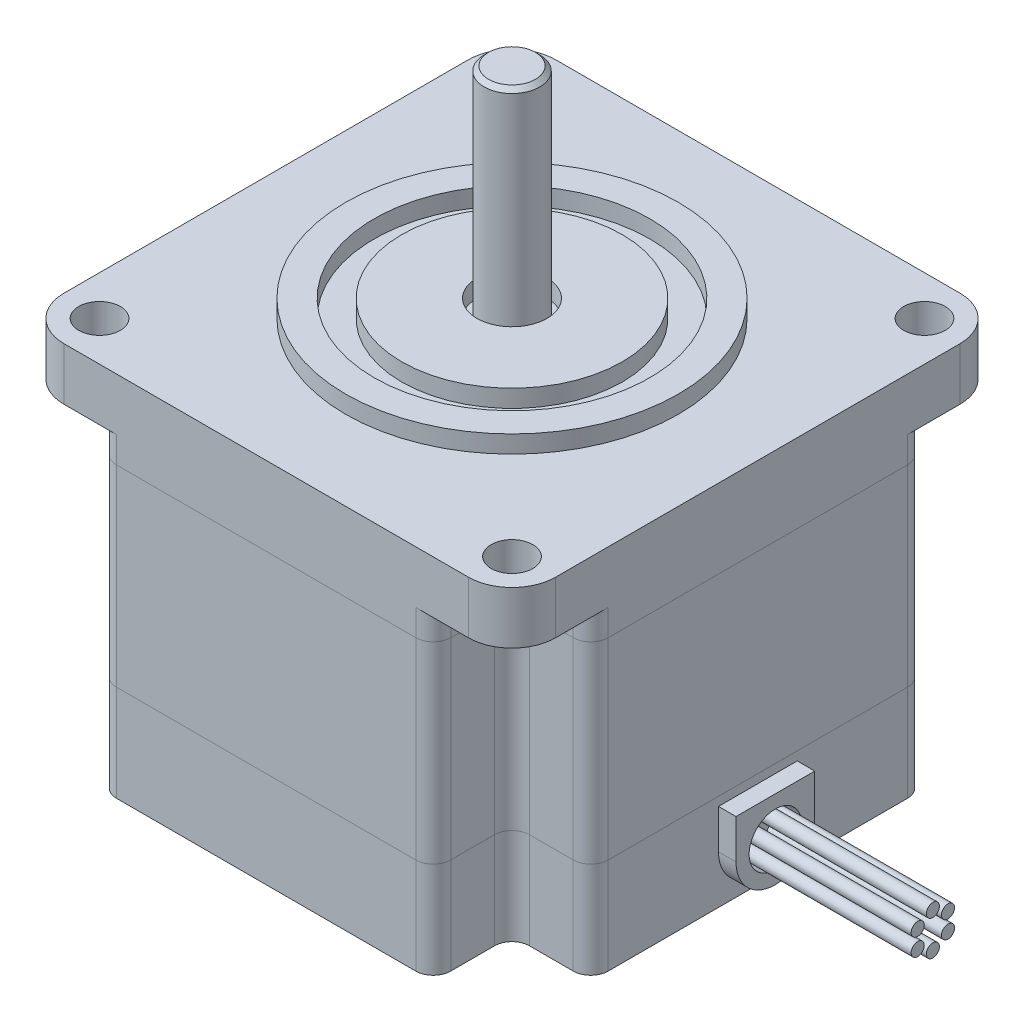
SolidWorks part; units mm, degrees
other "Camera1"
ref_plane "Front Plane" through (0, 0, 0) normal (0, 0, 1) x (1, 0, 0)
ref_plane "Top Plane" through (0, 0, 0) normal (0, 1, 0) x (1, 0, 0)
ref_plane "Right Plane" through (0, 0, 0) normal (1, 0, 0) x (0, 0, -1)
sketch "Sketch1" plane through (0, 0, 0) normal (0, 1, 0) x (1, 0, 0)
  line L1 (28.1, -28.1) -> (-28.1, -28.1)
  line L2 (28.1, -28.1) -> (28.1, 28.1)
  line L3 (28.1, 28.1) -> (-28.1, 28.1)
  line L4 (-28.1, -28.1) -> (-28.1, 28.1)
  line L5 (0, 28.1) -> (0, -28.1) construction
  line L6 (21, 0) -> (-28.1, 0) construction
  circle A0 centre (23.57, 23.57) radius 2.375
  circle A1 centre (23.57, -23.57) radius 2.375
  circle A2 centre (-23.57, -23.57) radius 2.375
  circle A3 centre (-23.57, 23.57) radius 2.375
  point P0 (0, 0)
  point P1 (-28.1, 28.1)
  point P6 (0, 28.1)
  point P7 (-28.1, 0)
  point P15 (0, 0)
  point P19 (0, -28.1)
  dimension "D2" = 4.75
  dimension "D1" = 56.2
  dimension "D4" = 47.14
  dimension "D3" = 4
extrude "Boss-Extrude2" add sketch "Sketch1" along normal blind 11
sketch "Sketch2" plane through (0, 11, 0) normal (0, 1, 0) x (1, 0, 0)
  line L8 (28.1, 28.1) -> (-28.1, 28.1)
  line L10 (-28.1, 28.1) -> (-28.1, -28.1)
  line L12 (-28.1, -28.1) -> (28.1, -28.1)
  line L14 (28.1, -28.1) -> (28.1, 28.1)
  line L16 (28.1, 28.1) -> (-28.1, 28.1)
  line L18 (-28.1, 28.1) -> (-28.1, -28.1)
  line L20 (-28.1, -28.1) -> (28.1, -28.1)
  line L22 (28.1, -28.1) -> (28.1, 28.1)
  circle A0 centre (-23.57, -23.57) radius 2.375 construction
  circle A1 centre (23.57, -23.57) radius 2.375 construction
  circle A2 centre (23.57, 23.57) radius 2.375 construction
  circle A3 centre (-23.57, 23.57) radius 2.375 construction
  circle A4 centre (-23.57, -23.57) radius 2.375
  circle A5 centre (23.57, -23.57) radius 2.375
  circle A6 centre (23.57, 23.57) radius 2.375
  circle A7 centre (-23.57, 23.57) radius 2.375
  dimension "D1" = 0
extrude "Boss-Extrude3" add sketch "Sketch2" along normal blind 22 separate body
sketch "Sketch3" plane through (0, 33, 0) normal (0, 1, 0) x (1, 0, 0)
  line L9 (28.1, 28.1) -> (-28.1, 28.1)
  line L11 (-28.1, 28.1) -> (-28.1, -28.1)
  line L13 (-28.1, -28.1) -> (28.1, -28.1)
  line L15 (28.1, -28.1) -> (28.1, 28.1)
  line L17 (28.1, 28.1) -> (-28.1, 28.1)
  line L19 (-28.1, 28.1) -> (-28.1, -28.1)
  line L21 (-28.1, -28.1) -> (28.1, -28.1)
  line L23 (28.1, -28.1) -> (28.1, 28.1)
  circle A0 centre (23.57, 23.57) radius 2.375 construction
  circle A1 centre (23.57, -23.57) radius 2.375 construction
  circle A2 centre (-23.57, -23.57) radius 2.375 construction
  circle A3 centre (-23.57, 23.57) radius 2.375 construction
  circle A4 centre (23.57, 23.57) radius 2.375
  circle A5 centre (23.57, -23.57) radius 2.375
  circle A6 centre (-23.57, -23.57) radius 2.375
  circle A7 centre (-23.57, 23.57) radius 2.375
  point P4 (0, 0)
  point P5 (0, 0)
  point P6 (0, 0)
  point P7 (0, 0)
  point P8 (0, 0)
  dimension "D1" = 0
extrude "Boss-Extrude4" add sketch "Sketch3" along normal blind 9 separate body
sketch "Sketch4" plane through (28.1, 0, 0) normal (1, 0, 0) x (0, 0, -1)
  line L1 (0, 0) -> (0, 11) construction
  line L2 (-28.1, 11) -> (28.1, 11) construction
  line L3 (-4.5, 5.5) -> (-4.5, 10)
  line L4 (-4.5, 10) -> (4.5, 10)
  line L5 (4.5, 5.5) -> (4.5, 10)
  arc A0 (-4.5, 5.5) -> (4.5, 5.5) centre (0, 5.5) ccw
  circle A1 centre (0, 5.5) radius 3
  point P11 (0, 10)
  dimension "D1" = 6
  dimension "D2" = 9
extrude "Boss-Extrude5" add sketch "Sketch4" along normal blind 2 separate body
sketch "Sketch5" plane through (28.1, 0, 0) normal (1, 0, 0) x (0, 0, -1)
  circle A0 centre (-1.7321, 4.5) radius 0.75
  circle A1 centre (0, 3.5) radius 0.75
  circle A2 centre (-1.7321, 6.5) radius 0.75
  circle A3 centre (0, 7.5) radius 0.75
  circle A4 centre (1.7321, 6.5) radius 0.75
  circle A5 centre (1.7321, 4.5) radius 0.75
  circle A6 centre (0, 5.5) radius 2 construction
  point P15 (0, 5.5)
  dimension "D1" = 1.5
  dimension "D3" = 4
  dimension "D2" = 6
extrude "Boss-Extrude6" add sketch "Sketch5" along normal blind 20 separate body contours A2 | A0 | A1 | A5 | A4 | A3
sketch "Sketch6" plane through (0, 42, 0) normal (0, 1, 0) x (1, 0, 0)
  circle A0 centre (0, 0) radius 12.6
  circle A1 centre (0, 0) radius 19
  circle A2 centre (0, 0) radius 15.75
  circle A3 centre (0, 0) radius 4
  dimension "D1" = 25.2
  dimension "D2" = 38
  dimension "D3" = 31.5
  dimension "D4" = 8
extrude "Boss-Extrude7" add sketch "Sketch6" along normal blind 2 contours A1 A2 | A0 region at (-12.2436, 42, 0) region at (-18.4626, 42, 0)
sketch "Sketch7" plane through (0, 42, 0) normal (0, 1, 0) x (1, 0, 0)
  circle A0 centre (0, 0) radius 3.175
  dimension "D1" = 6.35
extrude "Boss-Extrude8" add sketch "Sketch7" along normal blind 25 separate body
sketch "Sketch8" plane through (0, 67, 0) normal (0, 1, 0) x (1, 0, 0)
  circle A0 centre (0, 0) radius 7.675
  circle A1 centre (0, 0) radius 3.175
  circle A2 centre (0, 0) radius 3.175
  dimension "D2" = 15.35
  dimension "D1" = 0
extrude "Boss-Extrude9" [suppressed] add sketch "Sketch8" against normal blind 10 separate body
sketch "Sketch9" [suppressed] plane through (0, 56, 0) normal (0, -1, 0) x (1, 0, 0)
  circle A0 centre (0, 0) radius 10
  dimension "D1" = 20
extrude "Boss-Extrude10" [suppressed] add sketch "Sketch9" against normal blind 1
sketch "Sketch10" [suppressed] plane through (0, 66, 0) normal (0, 1, 0) x (1, 0, 0)
  line L0 (0, 7.675) -> (0, 8.675) construction
  line L1 (-0.6, 7.6515) -> (-0.3, 8.4658)
  line L2 (0.6, 7.6515) -> (0.3, 8.4658)
  line L3 (1.1177, 7.5932) -> (1.5913, 8.3203)
  line L4 (2.2876, 7.3262) -> (2.1763, 8.1868)
  line L5 (1.7078, 7.4826) -> (1.9304, 8.4575) construction
  line L6 (2.7793, 7.1541) -> (3.4029, 7.7576)
  line L7 (3.8604, 6.6334) -> (3.9435, 7.4973)
  line L8 (3.3301, 6.9149) -> (3.7639, 7.8159) construction
  line L9 (4.3015, 6.3563) -> (5.0438, 6.8059)
  line L10 (5.2397, 5.6081) -> (5.5129, 6.4318)
  line L11 (4.7853, 6.0006) -> (5.4088, 6.7824) construction
  line L12 (5.6081, 5.2397) -> (6.4318, 5.5129)
  line L13 (6.3563, 4.3015) -> (6.8059, 5.0438)
  line L14 (6.0006, 4.7853) -> (6.7824, 5.4088) construction
  line L15 (6.6334, 3.8604) -> (7.4973, 3.9435)
  line L16 (7.1541, 2.7793) -> (7.7576, 3.4029)
  line L17 (6.9149, 3.3301) -> (7.8159, 3.7639) construction
  line L18 (7.3262, 2.2876) -> (8.1868, 2.1763)
  line L19 (7.5932, 1.1177) -> (8.3203, 1.5913)
  line L20 (7.4826, 1.7078) -> (8.4575, 1.9304) construction
  line L21 (7.6515, 0.6) -> (8.4658, 0.3)
  line L22 (7.6515, -0.6) -> (8.4658, -0.3)
  line L23 (7.675, 0) -> (8.675, 0) construction
  line L24 (7.5932, -1.1177) -> (8.3203, -1.5913)
  line L25 (7.3262, -2.2876) -> (8.1868, -2.1763)
  line L26 (7.4826, -1.7078) -> (8.4575, -1.9304) construction
  line L27 (7.1541, -2.7793) -> (7.7576, -3.4029)
  line L28 (6.6334, -3.8604) -> (7.4973, -3.9435)
  line L29 (6.9149, -3.3301) -> (7.8159, -3.7639) construction
  line L30 (6.3563, -4.3015) -> (6.8059, -5.0438)
  line L31 (5.6081, -5.2397) -> (6.4318, -5.5129)
  line L32 (6.0006, -4.7853) -> (6.7824, -5.4088) construction
  line L33 (5.2397, -5.6081) -> (5.5129, -6.4318)
  line L34 (4.3015, -6.3563) -> (5.0438, -6.8059)
  line L35 (4.7853, -6.0006) -> (5.4088, -6.7824) construction
  line L36 (3.8604, -6.6334) -> (3.9435, -7.4973)
  line L37 (2.7793, -7.1541) -> (3.4029, -7.7576)
  line L38 (3.3301, -6.9149) -> (3.7639, -7.8159) construction
  line L39 (2.2876, -7.3262) -> (2.1763, -8.1868)
  line L40 (1.1177, -7.5932) -> (1.5913, -8.3203)
  line L41 (1.7078, -7.4826) -> (1.9304, -8.4575) construction
  line L42 (0.6, -7.6515) -> (0.3, -8.4658)
  line L43 (-0.6, -7.6515) -> (-0.3, -8.4658)
  line L44 (0, -7.675) -> (0, -8.675) construction
  line L45 (-1.1177, -7.5932) -> (-1.5913, -8.3203)
  line L46 (-2.2876, -7.3262) -> (-2.1763, -8.1868)
  line L47 (-1.7078, -7.4826) -> (-1.9304, -8.4575) construction
  line L48 (-2.7793, -7.1541) -> (-3.4029, -7.7576)
  line L49 (-3.8604, -6.6334) -> (-3.9435, -7.4973)
  line L50 (-3.3301, -6.9149) -> (-3.7639, -7.8159) construction
  line L51 (-4.3015, -6.3563) -> (-5.0438, -6.8059)
  line L52 (-5.2397, -5.6081) -> (-5.5129, -6.4318)
  line L53 (-4.7853, -6.0006) -> (-5.4088, -6.7824) construction
  line L54 (-5.6081, -5.2397) -> (-6.4318, -5.5129)
  line L55 (-6.3563, -4.3015) -> (-6.8059, -5.0438)
  line L56 (-6.0006, -4.7853) -> (-6.7824, -5.4088) construction
  line L57 (-6.6334, -3.8604) -> (-7.4973, -3.9435)
  line L58 (-7.1541, -2.7793) -> (-7.7576, -3.4029)
  line L59 (-6.9149, -3.3301) -> (-7.8159, -3.7639) construction
  line L60 (-7.3262, -2.2876) -> (-8.1868, -2.1763)
  line L61 (-7.5932, -1.1177) -> (-8.3203, -1.5913)
  line L62 (-7.4826, -1.7078) -> (-8.4575, -1.9304) construction
  line L63 (-7.6515, -0.6) -> (-8.4658, -0.3)
  line L64 (-7.6515, 0.6) -> (-8.4658, 0.3)
  line L65 (-7.675, 0) -> (-8.675, 0) construction
  line L66 (-7.5932, 1.1177) -> (-8.3203, 1.5913)
  line L67 (-7.3262, 2.2876) -> (-8.1868, 2.1763)
  line L68 (-7.4826, 1.7078) -> (-8.4575, 1.9304) construction
  line L69 (-7.1541, 2.7793) -> (-7.7576, 3.4029)
  line L70 (-6.6334, 3.8604) -> (-7.4973, 3.9435)
  line L71 (-6.9149, 3.3301) -> (-7.8159, 3.7639) construction
  line L72 (-6.3563, 4.3015) -> (-6.8059, 5.0438)
  line L73 (-5.6081, 5.2397) -> (-6.4318, 5.5129)
  line L74 (-6.0006, 4.7853) -> (-6.7824, 5.4088) construction
  line L75 (-5.2397, 5.6081) -> (-5.5129, 6.4318)
  line L76 (-4.3015, 6.3563) -> (-5.0438, 6.8059)
  line L77 (-4.7853, 6.0006) -> (-5.4088, 6.7824) construction
  line L78 (-3.8604, 6.6334) -> (-3.9435, 7.4973)
  line L79 (-2.7793, 7.1541) -> (-3.4029, 7.7576)
  line L80 (-3.3301, 6.9149) -> (-3.7639, 7.8159) construction
  line L81 (-2.2876, 7.3262) -> (-2.1763, 8.1868)
  line L82 (-1.1177, 7.5932) -> (-1.5913, 8.3203)
  line L83 (-1.7078, 7.4826) -> (-1.9304, 8.4575) construction
  circle A0 centre (0, 0) radius 8.675 construction
  circle A1 centre (0, 0) radius 7.675 construction
  circle A2 centre (0, 0) radius 7.675 construction
  arc A3 (-0.3, 8.4658) -> (0, 8.675) centre (0, 8.3553) cw
  circle A4 centre (0, 0) radius 7.675
  arc A5 (0.6, 7.6515) -> (-0.6, 7.6515) centre (0, 0) ccw
  arc A6 (0.3, 8.4658) -> (0, 8.675) centre (0, 8.3553) ccw
  arc A7 (1.5913, 8.3203) -> (1.9304, 8.4575) centre (1.8592, 8.1458) cw
  arc A8 (2.2876, 7.3262) -> (1.1177, 7.5932) centre (0, 0) ccw
  arc A9 (2.1763, 8.1868) -> (1.9304, 8.4575) centre (1.8592, 8.1458) ccw
  arc A10 (3.4029, 7.7576) -> (3.7639, 7.8159) centre (3.6252, 7.5279) cw
  arc A11 (3.8604, 6.6334) -> (2.7793, 7.1541) centre (0, 0) ccw
  arc A12 (3.9435, 7.4973) -> (3.7639, 7.8159) centre (3.6252, 7.5279) ccw
  arc A13 (5.0438, 6.8059) -> (5.4088, 6.7824) centre (5.2094, 6.5324) cw
  arc A14 (5.2397, 5.6081) -> (4.3015, 6.3563) centre (0, 0) ccw
  arc A15 (5.5129, 6.4318) -> (5.4088, 6.7824) centre (5.2094, 6.5324) ccw
  arc A16 (6.4318, 5.5129) -> (6.7824, 5.4088) centre (6.5324, 5.2094) cw
  arc A17 (6.3563, 4.3015) -> (5.6081, 5.2397) centre (0, 0) ccw
  arc A18 (6.8059, 5.0438) -> (6.7824, 5.4088) centre (6.5324, 5.2094) ccw
  arc A19 (7.4973, 3.9435) -> (7.8159, 3.7639) centre (7.5279, 3.6252) cw
  arc A20 (7.1541, 2.7793) -> (6.6334, 3.8604) centre (0, 0) ccw
  arc A21 (7.7576, 3.4029) -> (7.8159, 3.7639) centre (7.5279, 3.6252) ccw
  arc A22 (8.1868, 2.1763) -> (8.4575, 1.9304) centre (8.1458, 1.8592) cw
  arc A23 (7.5932, 1.1177) -> (7.3262, 2.2876) centre (0, 0) ccw
  arc A24 (8.3203, 1.5913) -> (8.4575, 1.9304) centre (8.1458, 1.8592) ccw
  arc A25 (8.4658, 0.3) -> (8.675, 0) centre (8.3553, 0) cw
  arc A26 (7.6515, -0.6) -> (7.6515, 0.6) centre (0, 0) ccw
  arc A27 (8.4658, -0.3) -> (8.675, 0) centre (8.3553, 0) ccw
  arc A28 (8.3203, -1.5913) -> (8.4575, -1.9304) centre (8.1458, -1.8592) cw
  arc A29 (7.3262, -2.2876) -> (7.5932, -1.1177) centre (0, 0) ccw
  arc A30 (8.1868, -2.1763) -> (8.4575, -1.9304) centre (8.1458, -1.8592) ccw
  arc A31 (7.7576, -3.4029) -> (7.8159, -3.7639) centre (7.5279, -3.6252) cw
  arc A32 (6.6334, -3.8604) -> (7.1541, -2.7793) centre (0, 0) ccw
  arc A33 (7.4973, -3.9435) -> (7.8159, -3.7639) centre (7.5279, -3.6252) ccw
  arc A34 (6.8059, -5.0438) -> (6.7824, -5.4088) centre (6.5324, -5.2094) cw
  arc A35 (5.6081, -5.2397) -> (6.3563, -4.3015) centre (0, 0) ccw
  arc A36 (6.4318, -5.5129) -> (6.7824, -5.4088) centre (6.5324, -5.2094) ccw
  arc A37 (5.5129, -6.4318) -> (5.4088, -6.7824) centre (5.2094, -6.5324) cw
  arc A38 (4.3015, -6.3563) -> (5.2397, -5.6081) centre (0, 0) ccw
  arc A39 (5.0438, -6.8059) -> (5.4088, -6.7824) centre (5.2094, -6.5324) ccw
  arc A40 (3.9435, -7.4973) -> (3.7639, -7.8159) centre (3.6252, -7.5279) cw
  arc A41 (2.7793, -7.1541) -> (3.8604, -6.6334) centre (0, 0) ccw
  arc A42 (3.4029, -7.7576) -> (3.7639, -7.8159) centre (3.6252, -7.5279) ccw
  arc A43 (2.1763, -8.1868) -> (1.9304, -8.4575) centre (1.8592, -8.1458) cw
  arc A44 (1.1177, -7.5932) -> (2.2876, -7.3262) centre (0, 0) ccw
  arc A45 (1.5913, -8.3203) -> (1.9304, -8.4575) centre (1.8592, -8.1458) ccw
  arc A46 (0.3, -8.4658) -> (0, -8.675) centre (0, -8.3553) cw
  arc A47 (-0.6, -7.6515) -> (0.6, -7.6515) centre (0, 0) ccw
  arc A48 (-0.3, -8.4658) -> (0, -8.675) centre (0, -8.3553) ccw
  arc A49 (-1.5913, -8.3203) -> (-1.9304, -8.4575) centre (-1.8592, -8.1458) cw
  arc A50 (-2.2876, -7.3262) -> (-1.1177, -7.5932) centre (0, 0) ccw
  arc A51 (-2.1763, -8.1868) -> (-1.9304, -8.4575) centre (-1.8592, -8.1458) ccw
  arc A52 (-3.4029, -7.7576) -> (-3.7639, -7.8159) centre (-3.6252, -7.5279) cw
  arc A53 (-3.8604, -6.6334) -> (-2.7793, -7.1541) centre (0, 0) ccw
  arc A54 (-3.9435, -7.4973) -> (-3.7639, -7.8159) centre (-3.6252, -7.5279) ccw
  arc A55 (-5.0438, -6.8059) -> (-5.4088, -6.7824) centre (-5.2094, -6.5324) cw
  arc A56 (-5.2397, -5.6081) -> (-4.3015, -6.3563) centre (0, 0) ccw
  arc A57 (-5.5129, -6.4318) -> (-5.4088, -6.7824) centre (-5.2094, -6.5324) ccw
  arc A58 (-6.4318, -5.5129) -> (-6.7824, -5.4088) centre (-6.5324, -5.2094) cw
  arc A59 (-6.3563, -4.3015) -> (-5.6081, -5.2397) centre (0, 0) ccw
  arc A60 (-6.8059, -5.0438) -> (-6.7824, -5.4088) centre (-6.5324, -5.2094) ccw
  arc A61 (-7.4973, -3.9435) -> (-7.8159, -3.7639) centre (-7.5279, -3.6252) cw
  arc A62 (-7.1541, -2.7793) -> (-6.6334, -3.8604) centre (0, 0) ccw
  arc A63 (-7.7576, -3.4029) -> (-7.8159, -3.7639) centre (-7.5279, -3.6252) ccw
  arc A64 (-8.1868, -2.1763) -> (-8.4575, -1.9304) centre (-8.1458, -1.8592) cw
  arc A65 (-7.5932, -1.1177) -> (-7.3262, -2.2876) centre (0, 0) ccw
  arc A66 (-8.3203, -1.5913) -> (-8.4575, -1.9304) centre (-8.1458, -1.8592) ccw
  arc A67 (-8.4658, -0.3) -> (-8.675, 0) centre (-8.3553, 0) cw
  arc A68 (-7.6515, 0.6) -> (-7.6515, -0.6) centre (0, 0) ccw
  arc A69 (-8.4658, 0.3) -> (-8.675, 0) centre (-8.3553, 0) ccw
  arc A70 (-8.3203, 1.5913) -> (-8.4575, 1.9304) centre (-8.1458, 1.8592) cw
  arc A71 (-7.3262, 2.2876) -> (-7.5932, 1.1177) centre (0, 0) ccw
  arc A72 (-8.1868, 2.1763) -> (-8.4575, 1.9304) centre (-8.1458, 1.8592) ccw
  arc A73 (-7.7576, 3.4029) -> (-7.8159, 3.7639) centre (-7.5279, 3.6252) cw
  arc A74 (-6.6334, 3.8604) -> (-7.1541, 2.7793) centre (0, 0) ccw
  arc A75 (-7.4973, 3.9435) -> (-7.8159, 3.7639) centre (-7.5279, 3.6252) ccw
  arc A76 (-6.8059, 5.0438) -> (-6.7824, 5.4088) centre (-6.5324, 5.2094) cw
  arc A77 (-5.6081, 5.2397) -> (-6.3563, 4.3015) centre (0, 0) ccw
  arc A78 (-6.4318, 5.5129) -> (-6.7824, 5.4088) centre (-6.5324, 5.2094) ccw
  arc A79 (-5.5129, 6.4318) -> (-5.4088, 6.7824) centre (-5.2094, 6.5324) cw
  arc A80 (-4.3015, 6.3563) -> (-5.2397, 5.6081) centre (0, 0) ccw
  arc A81 (-5.0438, 6.8059) -> (-5.4088, 6.7824) centre (-5.2094, 6.5324) ccw
  arc A82 (-3.9435, 7.4973) -> (-3.7639, 7.8159) centre (-3.6252, 7.5279) cw
  arc A83 (-2.7793, 7.1541) -> (-3.8604, 6.6334) centre (0, 0) ccw
  arc A84 (-3.4029, 7.7576) -> (-3.7639, 7.8159) centre (-3.6252, 7.5279) ccw
  arc A85 (-2.1763, 8.1868) -> (-1.9304, 8.4575) centre (-1.8592, 8.1458) cw
  arc A86 (-1.1177, 7.5932) -> (-2.2876, 7.3262) centre (0, 0) ccw
  arc A87 (-1.5913, 8.3203) -> (-1.9304, 8.4575) centre (-1.8592, 8.1458) ccw
  point P236 (0, 0)
  dimension "D1" = 17.35
  dimension "D2" = 0
  dimension "D3" = 1.2
  dimension "D5" = 0.6
  dimension "D4" = 28
extrude "Boss-Extrude12" [suppressed] add sketch "Sketch10" against normal blind 9
sketch "Sketch11" plane through (0, 0, 0) normal (0, -1, 0) x (1, 0, 0)
  line L0 (0, 21.8817) -> (0, 0) construction
  line L2 (0, 0) -> (43.9252, 0) construction
  line L4 (28.1, 23.6) -> (19.1, 23.6) construction
  line L5 (-28.1, 28.1) -> (-19.1, 28.1)
  line L6 (-28.1, 28.1) -> (-28.1, 19.1)
  line L7 (-28.1, 19.1) -> (-19.1, 19.1)
  line L8 (-19.1, 28.1) -> (-19.1, 19.1)
  line L9 (-23.6, 19.1) -> (-23.6, 28.1) construction
  line L10 (-28.1, 23.6) -> (-19.1, 23.6) construction
  line L11 (23.6, 19.1) -> (23.6, 28.1) construction
  line L12 (19.1, 28.1) -> (19.1, 19.1)
  line L13 (28.1, 19.1) -> (19.1, 19.1)
  line L14 (28.1, 28.1) -> (28.1, 19.1)
  line L15 (28.1, 28.1) -> (19.1, 28.1)
  line L16 (23.6, -19.1) -> (23.6, -28.1) construction
  line L17 (-28.1, -23.6) -> (-19.1, -23.6) construction
  line L18 (-23.6, -19.1) -> (-23.6, -28.1) construction
  line L19 (28.1, -23.6) -> (19.1, -23.6) construction
  line L20 (28.1, -28.1) -> (19.1, -28.1)
  line L21 (28.1, -28.1) -> (28.1, -19.1)
  line L22 (28.1, -19.1) -> (19.1, -19.1)
  line L23 (19.1, -28.1) -> (19.1, -19.1)
  line L24 (-19.1, -28.1) -> (-19.1, -19.1)
  line L25 (-28.1, -19.1) -> (-19.1, -19.1)
  line L26 (-28.1, -28.1) -> (-28.1, -19.1)
  line L27 (-28.1, -28.1) -> (-19.1, -28.1)
  point P20 (23.6, 23.6)
  point P38 (-23.6, -23.6)
  point P39 (23.6, -23.6)
  point P52 (-23.6, 23.6)
  dimension "D1" = 9
extrude "Cut-Extrude1" cut sketch "Sketch11" against normal offset from surface (36 mm away) 6 up to face at (0, 42, 19)
fillet "Fillet1" radius 5 4 edges at (-28.1, 39, 28.1) (28.1, 39, 28.1) (28.1, 39, -28.1) (-28.1, 39, -28.1)
fillet "Fillet2" radius 2 12 edges at (19.1, 5.5, -28.1) (19.1, 5.5, -19.1) (28.1, 5.5, -19.1) (-28.1, 5.5, -19.1) (-19.1, 5.5, -19.1) (-19.1, 5.5, -28.1) (-28.1, 5.5, 19.1) (-19.1, 5.5, 19.1) (-19.1, 5.5, 28.1) (28.1, 5.5, 19.1) (19.1, 5.5, 28.1) (19.1, 5.5, 19.1)
fillet "Fillet3" radius 2 12 edges at (28.1, 22, 19.1) (19.1, 22, 19.1) (19.1, 22, 28.1) (-19.1, 22, 28.1) (-19.1, 22, 19.1) (-28.1, 22, 19.1) (-28.1, 22, -19.1) (-19.1, 22, -19.1) (-19.1, 22, -28.1) (19.1, 22, -28.1) (28.1, 22, -19.1) (19.1, 22, -19.1)
chamfer "Chamfer1" distance 0.5 angle 45 1 edges at (0, 67, 3.175)
fillet "Fillet4" radius 2 12 edges at (19.1, 34.5, -28.1) (28.1, 34.5, -19.1) (19.1, 34.5, -19.1) (-19.1, 34.5, -28.1) (-19.1, 34.5, -19.1) (-28.1, 34.5, -19.1) (-28.1, 34.5, 19.1) (-19.1, 34.5, 19.1) (-19.1, 34.5, 28.1) (28.1, 34.5, 19.1) (19.1, 34.5, 19.1) (19.1, 34.5, 28.1)
